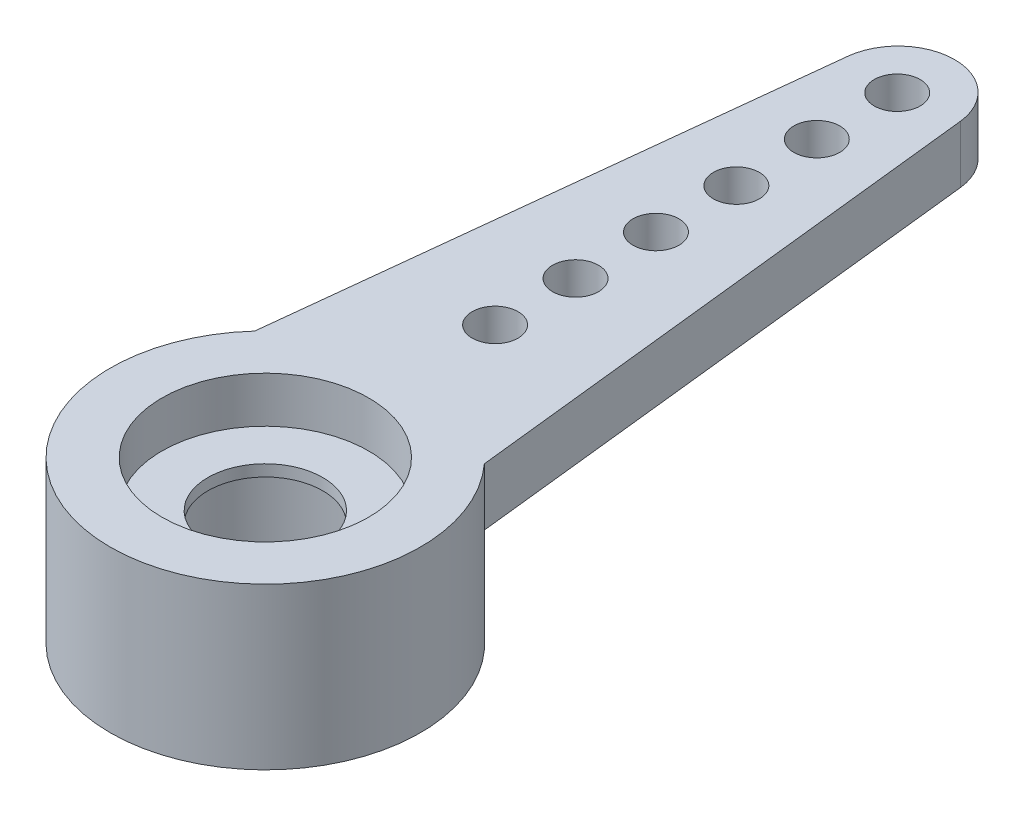
SolidWorks part; units mm, degrees
ref_plane "Front Plane" through (0, 0, 0) normal (0, 0, 1) x (1, 0, 0)
ref_plane "Top Plane" through (0, 0, 0) normal (0, 1, 0) x (1, 0, 0)
ref_plane "Right Plane" through (0, 0, 0) normal (1, 0, 0) x (0, 0, -1)
sketch "Sketch1" plane through (0, 0, 0) normal (0, 1, 0) x (1, 0, 0)
  circle A0 centre (0, 0) radius 2.286
  circle A1 centre (0, 0) radius 3.429
  dimension "D1" = 4.572
  dimension "D2" = 6.858
extrude "Boss-Extrude1" add sketch "Sketch1" along normal blind 3.556
sketch "Sketch2" plane through (0, 3.556, 0) normal (0, 1, 0) x (1, 0, 0)
  line L0 (0, 0) -> (0, 15.24) construction
  line L1 (-2.54, 2.3036) -> (-1.2445, 14.1244)
  line L2 (2.54, 2.3036) -> (1.2445, 14.1244)
  circle A0 centre (0, 0) radius 3.429 construction
  arc A1 (-1.2445, 14.1244) -> (0, 15.24) centre (0, 13.988) cw
  arc A2 (1.2445, 14.1244) -> (0, 15.24) centre (0, 13.988) ccw
  circle A3 centre (0, 0) radius 1.27
  circle A4 centre (0, 0) radius 2.286
  circle A5 centre (0, 0) radius 3.429
  circle M3 centre (0, 0) radius 3.429
  circle M4 centre (0, 0) radius 2.286
  dimension "D3" = 2.54
  dimension "D1" = 15.24
  dimension "D2" = 5.08
extrude "Boss-Extrude2" add sketch "Sketch2" against normal blind 1.27 contours A5 L0 A1 L1 | L0 L2 A2 M3 region at (-0.9605, 3.556, -8.3292) region at (0.9605, 3.556, -8.3292)
extrude "Boss-Extrude3" add sketch "Sketch2<3>" against normal blind 0.254 from offset 1.016 contours A3 M4 region at (-2.2213, 3.556, 0) offset against normal yes
sketch "Sketch2<3>" plane through (0, 3.556, 0) normal (0, 1, 0) x (1, 0, 0) same geometry as "Sketch2"
sketch "Sketch3" plane through (0, 3.556, 0) normal (0, 1, 0) x (1, 0, 0)
  line L0 (0, 0) -> (0, 15.24) construction
  circle A0 centre (0, 5.08) radius 0.508
  circle A1 centre (0, 5.08) radius 0.508
  circle A2 centre (0, 5.08) radius 0.508
  circle A3 centre (0, 5.08) radius 0.508
  circle A4 centre (0, 5.08) radius 0.508
  circle A5 centre (0, 5.08) radius 0.508
  dimension "D1" = 1.016
  dimension "D3" = 5.08
  dimension "D2" = 6
extrude "Cut-Extrude1" cut sketch "Sketch3" against normal through all contours A0 region at (0, 3.556, -5.08)
pattern_linear "LPattern1" count 6 spacing 1.778 along (0, 0, -1) of "Cut-Extrude1"
